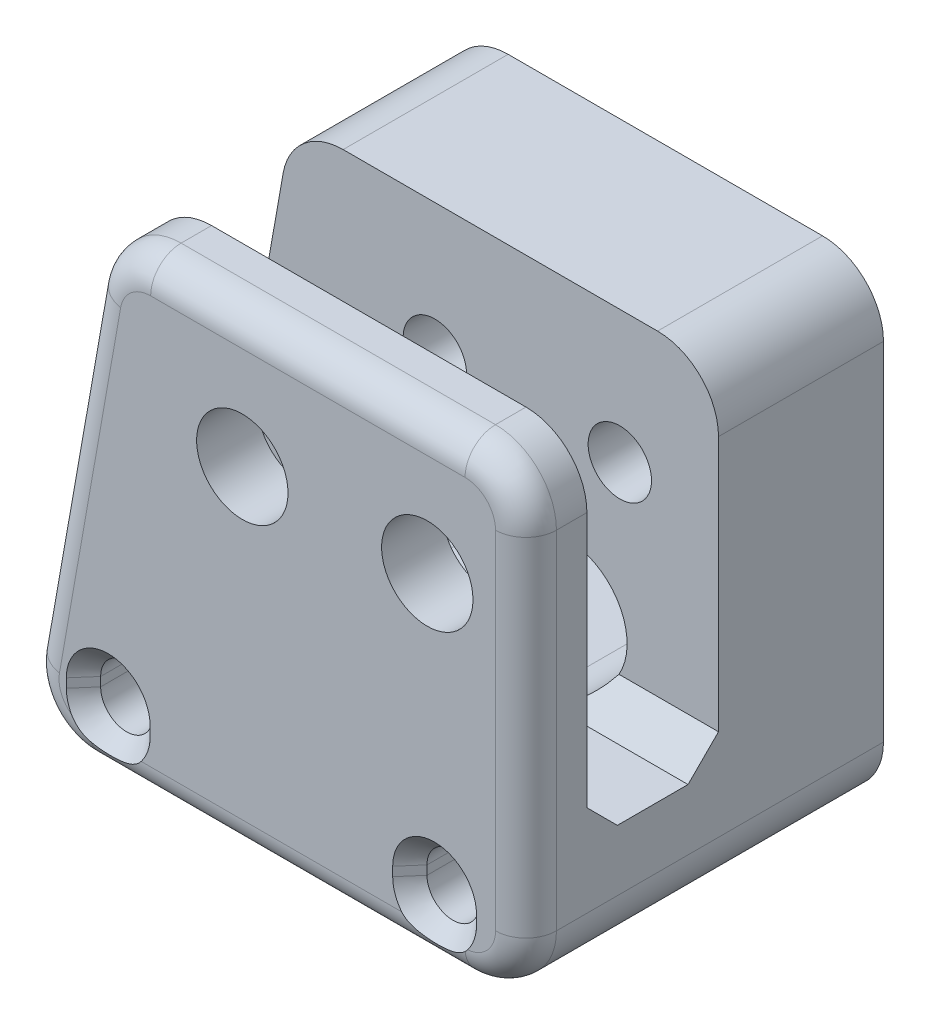
SolidWorks part; units mm, degrees
material "PET"
ref_plane "Front Plane" through (0, 0, 0) normal (0, 0, 1) x (1, 0, 0)
ref_plane "Top Plane" through (0, 0, 0) normal (0, 1, 0) x (1, 0, 0)
ref_plane "Right Plane" through (0, 0, 0) normal (1, 0, 0) x (0, 0, -1)
sketch "Sketch1" plane through (0, 0, 0) normal (0, 0, 1) x (1, 0, 0)
  line L0 (9.9949, 9.271) -> (9.9949, -24.688) construction
  line L2 (9.9949, 9.271) -> (9.9949, -15.163)
  line L3 (9.9949, 9.271) -> (-12.2301, 9.271)
  line L4 (-12.2301, 9.271) -> (-16.5385, -15.163)
  line L5 (-16.5385, -15.163) -> (9.9949, -15.163)
  dimension "D1" = 9.525
  dimension "D2" = 80
  dimension "D3" = 22.225
extrude "Boss-Extrude1" add sketch "Sketch1" along normal blind 3.175
extrude "Boss-Extrude2" add sketch "Sketch1<2>" against normal up to surface (8.5979 mm away) from offset 6.858 separate body offset against normal yes
sketch "Sketch1<2>" plane through (0, 0, 0) normal (0, 0, 1) x (1, 0, 0) same geometry as "Sketch1"
sketch "Sketch3" plane through (0, 0, -6.858) normal (0, 0, 1) x (1, 0, 0)
  line L0 (9.9949, 9.271) -> (9.9949, -15.163) construction
  line L1 (-16.5385, -15.163) -> (-12.2301, 9.271) construction
  line L2 (9.9949, -15.163) -> (-16.5385, -15.163) construction
  line L3 (9.9949, -8.813) -> (9.9949, -15.163)
  line L4 (-16.5385, -15.163) -> (-15.4188, -8.813)
  line L5 (9.9949, -15.163) -> (-16.5385, -15.163)
  line L6 (9.9949, -8.813) -> (-15.4188, -8.813)
  dimension "D1" = 6.35
extrude "Boss-Extrude3" add sketch "Sketch3" along normal up to surface (6.858 mm away) up to face at (-2.1947, -2.946, 0)
hole_wizard "CSK SLOT for #2 Flat Head Machine Screw1" positions "Sketch4" profile "Sketch5" size "#2" standard "ANSI Inch" slot yes end condition through all
sketch "Sketch4" plane through (0, 0, 3.175) normal (0, 0, 1) x (1, 0, 0)
  line L0 (5.2324, -13.5755) -> (5.2324, -10.4005) construction
  line L1 (9.9949, -15.163) -> (9.9949, 9.271) construction
  line L2 (-16.5385, -15.163) -> (9.9949, -15.163) construction
  point P0 (5.2324, -11.988)
  point P2 (-11.776, -11.988)
  dimension "D1" = 3.175
  dimension "D2" = 3.175
  dimension "D3" = 4.7625
  dimension "D4" = 4.7625
sketch "Sketch5" plane through (5.2324, -11.988, 3.175) normal (1, 0, 0) x (0, -1, 0)
  line L0 (0, 0) -> (0, 18.6309)
  line L1 (0, 18.6309) -> (1.3525, 18.6309)
  line L2 (1.3525, 18.6309) -> (1.3525, 0.9569)
  line L3 (1.3525, 0.9569) -> (2.1844, 0)
  line L5 (2.1844, 0) -> (0, 0)
  line L6 (-1.3525, 0.9569) -> (-2.1844, 0) construction
  line L11 (0, -6.35) -> (0, 107.95) construction
  dimension "Thru Hole Dia." = 2.7051
  dimension "Thru Hole Depth" = 18.6309
  dimension "Near C'Sink Dia." = 4.3688
  dimension "Near C'Sink Angle" = 82
fillet "Fillet1" radius 3.175 6 edges at (-12.2301, 9.271, -11.157) (-12.2301, 9.271, 1.5875) (9.9949, 9.271, 1.5875) (9.9949, 9.271, -11.157) (9.9949, -15.163, -6.1405) (-16.5385, -15.163, -6.1405)
chamfer "Chamfer1" distance 1.5875 angle 45 2 edges at (-2.7119, -8.813, 0) (-2.7119, -8.813, -6.858)
hole_wizard "3/16 (0.1875) Diameter Hole1" positions "Sketch6" profile "Sketch7" hole size "3/16" standard "ANSI Inch" end condition up to next
sketch "Sketch6" plane through (0, 0, 3.175) normal (0, 0, 1) x (1, 0, 0)
  point P0 (4.8514, 2.3622)
  point P3 (-4.7879, 2.3622)
sketch "Sketch7" plane through (4.8514, 2.3622, 3.175) normal (1, 0, 0) x (0, -1, 0)
  line L0 (0, 0) -> (0, 3.175)
  line L1 (0, 3.175) -> (2.3812, 3.175)
  line L2 (2.3812, 3.175) -> (2.3812, 0)
  line L5 (2.3812, 0) -> (0, 0)
  line L11 (0, -6.35) -> (0, 107.95) construction
  dimension "Thru Hole Dia." = 4.7625
  dimension "Thru Hole Depth" = 3.175
hole_wizard "#0 Clearance Hole1" positions "Sketch8" profile "Sketch9" hole size "#0" standard "ANSI Inch" end condition up to next
sketch "Sketch8" plane through (0, 0, -15.4559) normal (0, 0, -1) x (-1, 0, 0)
  circle A0 centre (4.7879, 2.3622) radius 2.3812 construction
  circle A1 centre (-4.8514, 2.3622) radius 2.3812 construction
  point P0 (-4.8514, 2.3622)
  point P2 (4.7879, 2.3622)
sketch "Sketch9" plane through (4.8514, 2.3622, -15.4559) normal (1, 0, 0) x (0, 1, 0)
  line L0 (0, 0) -> (0, 8.5979)
  line L1 (0, 8.5979) -> (0.9271, 8.5979)
  line L2 (0.9271, 8.5979) -> (0.9271, 0)
  line L5 (0.9271, 0) -> (0, 0)
  line L11 (0, -6.35) -> (0, 107.95) construction
  dimension "Thru Hole Dia." = 1.8542
  dimension "Thru Hole Depth" = 8.5979
hole_wizard "Hole1" positions "Sketch10" profile "Sketch11" legacy
sketch "Sketch10" plane through (0, 0, -6.858) normal (0, 0, 1) x (1, 0, 0)
  point P0 (4.8514, 2.3622)
  point P3 (-4.7879, 2.3622)
sketch "Sketch11" plane through (4.8514, 2.3622, -6.858) normal (1, 0, 0) x (0, -1, 0)
  line L0 (0, 0) -> (0, 3.048)
  line L1 (0, 3.048) -> (1.524, 3.048)
  line L2 (1.524, 3.048) -> (1.651, 0)
  line L3 (1.651, 0) -> (0, 0)
  line L4 (0, 110) -> (0, -10) construction
  point P2 (0, 0)
  dimension "Minor Diameter" = 3.048
  dimension "Depth" = 3.048
  dimension "Major Diameter" = 3.302
sketch "Sketch13" plane through (0, 0, -15.4559) normal (0, 0, -1) x (-1, 0, 0)
  line L0 (-2.0574, -5.638) -> (6.848, -5.638) construction
  line L1 (-2.0574, -2.463) -> (6.848, -2.463)
  line L2 (-2.0574, -8.813) -> (6.848, -8.813)
  line L3 (15.8814, -11.4367) -> (12.6927, 6.6473) construction
  line L4 (-9.9949, 6.096) -> (-9.9949, -11.988) construction
  line L5 (15.4188, -8.813) -> (-9.9949, -8.813) construction
  arc A0 (-2.0574, -2.463) -> (-2.0574, -8.813) centre (-2.0574, -5.638) ccw
  arc A1 (6.848, -8.813) -> (6.848, -2.463) centre (6.848, -5.638) ccw
  point P2 (2.3953, -5.638)
  point P7 (-5.2324, -5.638)
  point P8 (10.023, -5.638)
  dimension "D1" = 4.7625
  dimension "D2" = 4.7625
  dimension "D3" = 6.35
extrude "Cut-Extrude2" cut sketch "Sketch13" against normal up to next
fillet "Fillet3" radius 1.5875 8 edges at (9.065, -14.2331, 3.175) (-2.9674, -15.163, 3.175) (-15.1868, -14.0288, 3.175) (-14.2871, -2.3947, 3.175) (-11.6068, 8.5282, 3.175) (-1.373, 9.271, 3.175) (9.065, 8.3411, 3.175) (9.9949, -2.946, 3.175)
